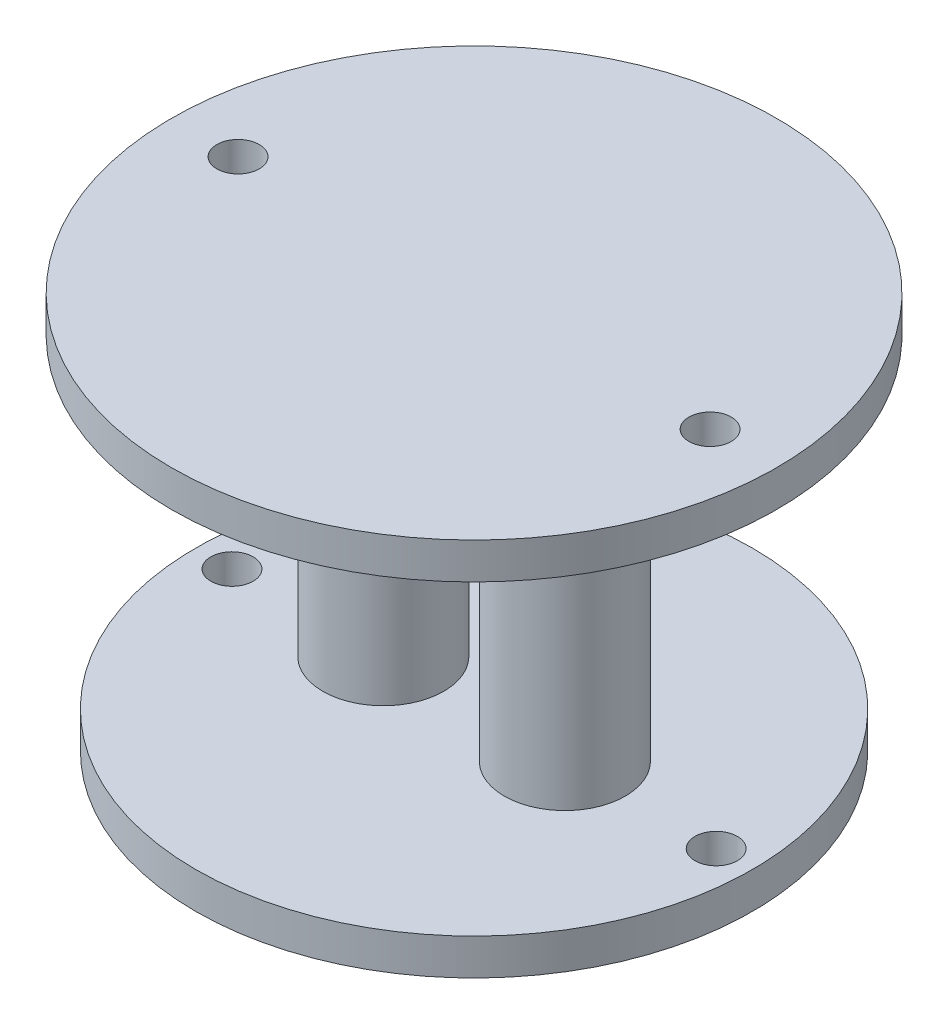
SolidWorks part; units mm, degrees
note: The reader was unsure of these and kept them because the rebuilt part matched: shared geometry of "草图1<3>".
ref_plane "前视基准面" through (0, 0, 0) normal (0, 0, 1) x (1, 0, 0)
ref_plane "上视基准面" through (0, 0, 0) normal (0, 1, 0) x (1, 0, 0)
ref_plane "右视基准面" through (0, 0, 0) normal (1, 0, 0) x (0, 0, -1)
sketch "草图1" plane through (0, 0, 0) normal (0, 1, 0) x (1, 0, 0)
  circle A0 centre (0, 0) radius 5
  circle A2 centre (15, 0) radius 5
  circle A4 centre (30, 0) radius 5 [skipped]
  circle A5 centre (7.5, 0) radius 23
  circle A6 centre (-12.5, 0) radius 1.75
  circle A7 centre (-12.5, 0) radius 1.75
  circle A8 centre (27.5, 0) radius 1.75
  dimension "D1" = 10
  dimension "D2" = 3
  dimension "D3" = 15
  dimension "D4" = 46
  dimension "D6" = 3.5
  dimension "D8" = 3.5
  dimension "D5" = 7.5
  dimension "D7" = 12.5
  dimension "D9" = 27.5
extrude "凸台-拉伸1" add sketch "草图1" along normal blind 3 contours A5 A8 A6 A0 A2
extrude "凸台-拉伸2" add sketch "草图1<3>" along normal blind 32.75 contours A0 | A2
sketch "草图1<3>" plane through (0, 0, 0) normal (0, 1, 0) x (1, 0, 0) same geometry as "草图1"
sketch "草图2" plane through (0, 32.75, 0) normal (0, 1, 0) x (1, 0, 0)
  circle A0 centre (7.5, 0) radius 25
  circle A1 centre (-12, 0) radius 1.75
  circle A2 centre (27, 0) radius 1.75
  point P6 (0, 0)
  point P7 (0, 0)
  dimension "D1" = 50
  dimension "D2" = 3.5
extrude "凸台-拉伸3" add sketch "草图2" against normal blind 3
